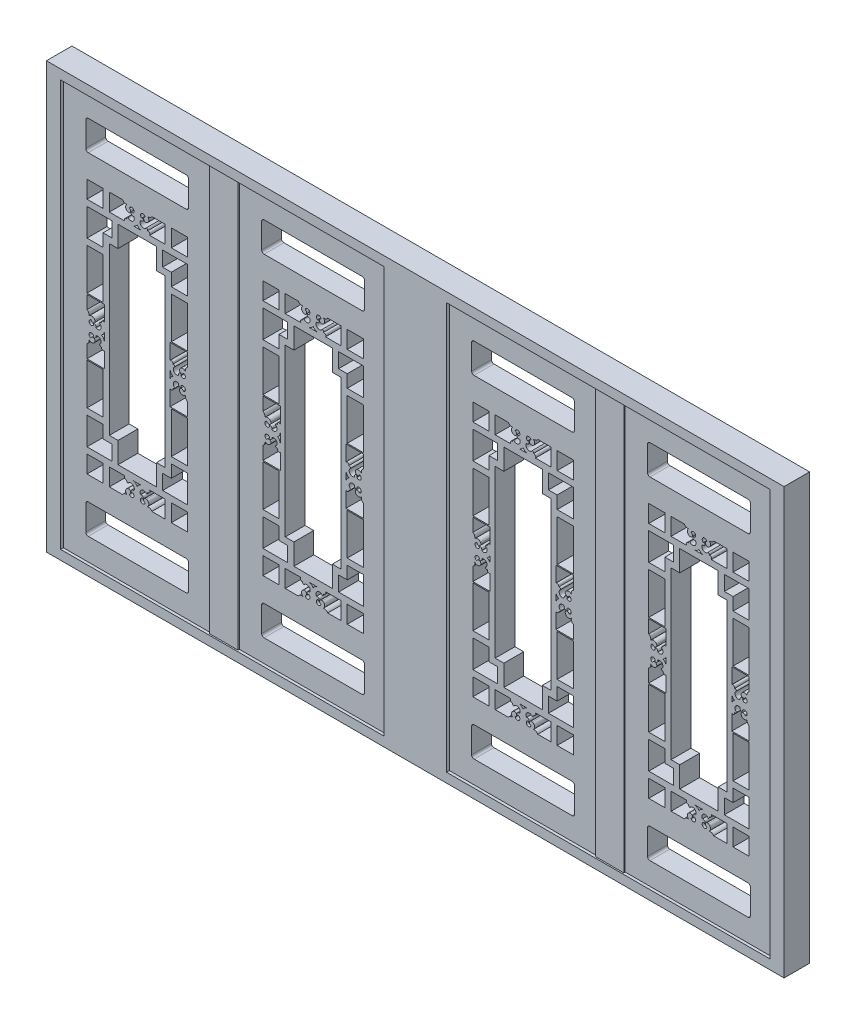
SolidWorks part; units mm, degrees
material "松木"
ref_plane "前视基准面" through (0, 0, 0) normal (0, 0, 1) x (1, 0, 0)
ref_plane "上视基准面" through (0, 0, 0) normal (0, 1, 0) x (1, 0, 0)
ref_plane "右视基准面" through (0, 0, 0) normal (1, 0, 0) x (0, 0, -1)
sketch "Sketch1" plane through (0, 0, 0) normal (0, 0, 1) x (1, 0, 0)
  line L0 (0, 0) -> (0, 1640)
  line L1 (0, 1640) -> (595, 1640)
  line L2 (595, 1640) -> (595, 0)
  line L3 (595, 0) -> (0, 0)
  dimension "D1" = 1640
  dimension "D2" = 595
extrude "Boss-Extrude1" add sketch "Sketch1" along normal blind 180
sketch "Sketch2" plane through (0, 0, 0) normal (0, 0, -1) x (-1, 0, 0)
  line L0 (-525, 1570) -> (-525, 70)
  line L1 (-525, 70) -> (-70, 70)
  line L2 (-70, 70) -> (-70, 1570)
  line L3 (-70, 1570) -> (-525, 1570)
  line L4 (-595, 0) -> (-595, 1640) construction
  line L5 (-595, 1640) -> (0, 1640) construction
  line L6 (-70, 1410) -> (-525, 1410)
  line L7 (-525, 230) -> (-70, 230)
  line L8 (-70, 1360) -> (-525, 1360)
  line L9 (-70, 280) -> (-525, 280)
  line L10 (-500, 1335) -> (-500, 305)
  line L11 (-500, 305) -> (-95, 305)
  line L12 (-95, 305) -> (-95, 1335)
  line L13 (-95, 1335) -> (-500, 1335)
  line L14 (-95, 1265) -> (-500, 1265)
  line L15 (-95, 1240) -> (-500, 1240)
  line L16 (-95, 375) -> (-500, 375)
  line L17 (-95, 400) -> (-500, 400)
  line L18 (-160, 1335) -> (-160, 1265)
  line L19 (-435, 1335) -> (-435, 1265)
  line L20 (-410, 1335) -> (-410, 1265)
  line L21 (-185, 1335) -> (-185, 1265)
  line L22 (-435, 375) -> (-435, 305)
  line L23 (-410, 375) -> (-410, 305)
  line L24 (-160, 375) -> (-160, 305)
  line L25 (-185, 375) -> (-185, 305)
  line L26 (-195, 400) -> (-195, 460)
  line L27 (-195, 460) -> (-160, 460)
  line L28 (-160, 460) -> (-160, 1180)
  line L29 (-160, 1180) -> (-195, 1180)
  line L30 (-195, 1180) -> (-195, 1240)
  line L31 (-400, 1240) -> (-400, 1180)
  line L32 (-400, 1180) -> (-435, 1180)
  line L33 (-435, 1180) -> (-435, 460)
  line L34 (-435, 460) -> (-400, 460)
  line L35 (-400, 460) -> (-400, 400)
  line L36 (-220, 1240) -> (-220, 1155)
  line L37 (-220, 1155) -> (-185, 1155)
  line L38 (-185, 1155) -> (-185, 485)
  line L39 (-185, 485) -> (-220, 485)
  line L40 (-220, 485) -> (-220, 400)
  line L41 (-375, 1240) -> (-375, 1155)
  line L42 (-375, 1155) -> (-410, 1155)
  line L43 (-410, 1155) -> (-410, 485)
  line L44 (-410, 485) -> (-375, 485)
  line L45 (-375, 485) -> (-375, 400)
  line L46 (-435, 1129) -> (-500, 1129)
  line L47 (-435, 1104) -> (-500, 1104)
  line L48 (-160, 1129) -> (-95, 1129)
  line L49 (-160, 1104) -> (-95, 1104)
  line L50 (-435, 511) -> (-500, 511)
  line L51 (-435, 536) -> (-500, 536)
  line L52 (-160, 511) -> (-95, 511)
  line L53 (-160, 536) -> (-95, 536)
  line L54 (-435, 937) -> (-500, 937)
  line L55 (-435, 919.4131) -> (-500, 919.4131)
  line L56 (-435, 703) -> (-500, 703)
  line L57 (-435, 728) -> (-500, 728)
  line L58 (-160, 919.4131) -> (-95, 919.4131)
  line L59 (-160, 937) -> (-95, 937)
  line L60 (-160, 703) -> (-95, 703)
  line L61 (-160, 728) -> (-95, 728)
  line L62 (-495, 210) -> (-100, 210)
  line L63 (-90, 200) -> (-90, 100)
  line L64 (-100, 90) -> (-495, 90)
  line L65 (-505, 100) -> (-505, 200)
  line L67 (-495, 1550) -> (-100, 1550)
  line L68 (-505, 1540) -> (-505, 1440)
  line L69 (-495, 1430) -> (-100, 1430)
  line L70 (-90, 1540) -> (-90, 1440)
  arc A0 (-495, 210) -> (-505, 200) centre (-495, 200) ccw
  arc A1 (-90, 200) -> (-100, 210) centre (-100, 200) ccw
  arc A2 (-505, 100) -> (-495, 90) centre (-495, 100) ccw
  arc A3 (-100, 90) -> (-90, 100) centre (-100, 100) ccw
  arc A4 (-495, 1550) -> (-505, 1540) centre (-495, 1540) ccw
  arc A5 (-90, 1540) -> (-100, 1550) centre (-100, 1540) ccw
  arc A6 (-505, 1440) -> (-495, 1430) centre (-495, 1440) ccw
  arc A7 (-100, 1430) -> (-90, 1440) centre (-100, 1440) ccw
  point P62 (-177.5, 1180)
  point P63 (-220, 442.5)
  point P64 (-177.5, 460)
  point P71 (-392.5, 485)
  dimension "D53" = 20
  dimension "D56" = 20
  dimension "D57" = 20
  dimension "D58" = 20
  dimension "D47" = 30
  dimension "D63" = 20
  dimension "D64" = 20
  dimension "D65" = 20
  dimension "D66" = 20
  dimension "D1" = 70
  dimension "D2" = 70
  dimension "D3" = 1500
  dimension "D4" = 455
  dimension "D5" = 160
  dimension "D6" = 160
  dimension "D7" = 50
  dimension "D8" = 50
  dimension "D9" = 25
  dimension "D10" = 25
  dimension "D11" = 25
  dimension "D12" = 25
  dimension "D13" = 70
  dimension "D14" = 25
  dimension "D15" = 25
  dimension "D16" = 70
  dimension "D17" = 65
  dimension "D18" = 65
  dimension "D19" = 25
  dimension "D20" = 25
  dimension "D21" = 100
  dimension "D22" = 100
  dimension "D23" = 60
  dimension "D24" = 60
  dimension "D25" = 35
  dimension "D26" = 35
  dimension "D27" = 100
  dimension "D28" = 35
  dimension "D29" = 60
  dimension "D30" = 60
  dimension "D31" = 25
  dimension "D32" = 25
  dimension "D33" = 25
  dimension "D34" = 25
  dimension "D35" = 25
  dimension "D36" = 25
  dimension "D37" = 25
  dimension "D38" = 25
  dimension "D39" = 111
  dimension "D40" = 25
  dimension "D41" = 111
  dimension "D42" = 25
  dimension "D43" = 167
  dimension "D44" = 17.5869
  dimension "D45" = 25
  dimension "D46" = 167
  dimension "D48" = 30
  dimension "D49" = 20
  dimension "D50" = 30
  dimension "D51" = 10
  dimension "D52" = 10
  dimension "D54" = 10
  dimension "D55" = 10
  dimension "D59" = 20
  dimension "D60" = 20
  dimension "D61" = 20
  dimension "D62" = 20
  dimension "D67" = 30
  dimension "D68" = 30
  dimension "D69" = 30
  dimension "D70" = 30
  dimension "D71" = 30
  dimension "D72" = 30
  dimension "D73" = 30
  dimension "D74" = 30
sketch "草图1" plane through (0, 0, 0) normal (0, 0, -1) x (-1, 0, 0)
  line L0 (-500, 305) -> (-95, 305) construction
  line L1 (-95, 375) -> (-500, 375) construction
  line L2 (-410, 375) -> (-410, 305) construction
  line L3 (-185, 375) -> (-185, 305) construction
  line L6 (-347.4491, 375) -> (-315.5, 375)
  line L7 (-279.5, 375) -> (-247.5509, 375)
  line L8 (-356.6733, 305) -> (-238.3267, 305)
  line L9 (-347.4491, 375) -> (-410, 375)
  line L10 (-410, 375) -> (-410, 305)
  line L11 (-410, 305) -> (-356.6733, 305)
  line L12 (-315.5, 375) -> (-279.5, 375)
  line L13 (-238.3267, 305) -> (-185, 305)
  line L14 (-185, 305) -> (-185, 375)
  line L15 (-185, 375) -> (-247.5509, 375)
  line L16 (-500, 707.5) -> (-430, 707.5)
  line L18 (-430, 802) -> (-430, 838)
  line L19 (-430, 707.5) -> (-430, 770.0509)
  line L20 (-430, 932.5) -> (-500, 932.5)
  line L22 (-500, 760.8267) -> (-500, 707.5)
  line L24 (-430, 869.9491) -> (-430, 932.5)
  line L25 (-500, 932.5) -> (-500, 879.1733)
  line L26 (-500, 879.1733) -> (-500, 1640) construction
  line L27 (-595, 707.5) -> (0, 707.5) construction
  line L28 (-595, 0) -> (-595, 1640) construction
  line L29 (0, 1640) -> (0, 0) construction
  line L30 (-500, 0) -> (-500, 760.8267) construction
  line L31 (0, 0) -> (-595, 0) construction
  line L32 (-595, 1640) -> (0, 1640) construction
  arc A0 (-297.5, 362.9626) -> (-315.5, 375) centre (-316.8257, 353.5409) ccw
  arc A1 (-279.5, 375) -> (-297.5, 362.9626) centre (-278.1743, 353.5409) ccw
  arc A2 (-311.5772, 341.0539) -> (-334.4772, 355.321) centre (-322.7578, 348.6199) ccw
  arc A4 (-260.5228, 355.321) -> (-283.4228, 341.0539) centre (-272.2422, 348.6199) ccw
  arc A5 (-347.4491, 375) -> (-339.4787, 363.4423) centre (-341.29, 370.7203) ccw
  arc A6 (-255.5213, 363.4423) -> (-247.5509, 375) centre (-253.71, 370.7203) ccw
  arc A7 (-339.4787, 363.4423) -> (-334.4772, 355.321) centre (-333.2172, 361.6977) ccw
  arc A8 (-260.5228, 355.321) -> (-255.5213, 363.4423) centre (-261.7828, 361.6977) ccw
  arc A9 (-297.5, 336.0027) -> (-311.5772, 341.0539) centre (-304.7324, 337.9882) ccw
  arc A10 (-283.4228, 341.0539) -> (-297.5, 336.0027) centre (-290.2676, 337.9882) ccw
  arc A11 (-311.5772, 341.0539) -> (-320.3587, 328.3114) centre (-314.2948, 333.5296) ccw
  arc A12 (-274.6413, 328.3114) -> (-283.4228, 341.0539) centre (-280.7052, 333.5296) ccw
  arc A13 (-315.214, 331.0064) -> (-320.3587, 328.3114) centre (-316.5099, 327.2221) ccw
  arc A14 (-274.6413, 328.3114) -> (-279.786, 331.0064) centre (-278.4901, 327.2221) ccw
  arc A16 (-279.786, 331.0064) -> (-265.6848, 320.9352) centre (-275, 322.8) ccw
  arc A17 (-329.3152, 320.9352) -> (-334.7689, 337.0364) centre (-332, 329) ccw
  arc A18 (-260.2311, 337.0364) -> (-265.6848, 320.9352) centre (-263, 329) ccw
  arc A19 (-329.3152, 320.9352) -> (-315.214, 331.0064) centre (-320, 322.8) ccw
  arc A20 (-463.9461, 834.0772) -> (-476.6886, 842.8587) centre (-471.4704, 836.7948) ccw
  arc A21 (-334.7689, 337.0364) -> (-338.5296, 312.5413) centre (-330.2084, 323.8) ccw
  arc A23 (-338.5296, 312.5413) -> (-356.6733, 305) centre (-343, 297.7) ccw
  arc A24 (-238.3267, 305) -> (-256.4704, 312.5413) centre (-252, 297.7) ccw
  arc A25 (-256.4704, 312.5413) -> (-260.2311, 337.0364) centre (-264.7916, 323.8) ccw
  arc A26 (-473.9936, 837.714) -> (-476.6886, 842.8587) centre (-477.7779, 839.0099) ccw
  arc A27 (-463.9461, 805.9228) -> (-462.5046, 806.773) centre (-467.0118, 812.7676) ccw
  arc A28 (-484.0648, 851.8152) -> (-467.9636, 857.2689) centre (-476, 854.5) ccw
  arc A29 (-430, 869.9491) -> (-441.5577, 861.9787) centre (-434.2797, 863.79) ccw
  arc A30 (-467.9636, 857.2689) -> (-492.4587, 861.0296) centre (-481.2, 852.7084) ccw
  arc A31 (-442.0374, 820) -> (-430, 838) centre (-451.4591, 839.3257) ccw
  arc A32 (-441.5577, 861.9787) -> (-449.679, 856.9772) centre (-443.3023, 855.7172) ccw
  arc A33 (-467.9636, 782.7311) -> (-484.0648, 788.1848) centre (-476, 785.5) ccw
  arc A34 (-476.6886, 797.1413) -> (-463.9461, 805.9228) centre (-471.4704, 803.2052) ccw
  arc A35 (-476.6886, 797.1413) -> (-473.9936, 802.286) centre (-477.7779, 800.9901) ccw
  arc A36 (-441.5577, 778.0213) -> (-430, 770.0509) centre (-434.2797, 776.21) ccw
  arc A37 (-492.4587, 778.9704) -> (-467.9636, 782.7311) centre (-481.2, 787.2916) ccw
  arc A38 (-449.679, 783.0228) -> (-463.9461, 805.9228) centre (-456.3801, 794.7422) ccw
  arc A39 (-484.0648, 851.8152) -> (-473.9936, 837.714) centre (-482.2, 842.5) ccw
  arc A40 (-500, 760.8267) -> (-492.4587, 778.9704) centre (-507.3, 774.5) ccw
  arc A41 (-449.679, 783.0228) -> (-441.5577, 778.0213) centre (-443.3023, 784.2828) ccw
  arc A42 (-473.9936, 802.286) -> (-484.0648, 788.1848) centre (-482.2, 797.5) ccw
  arc A43 (-463.9461, 834.0772) -> (-449.679, 856.9772) centre (-456.3801, 845.2578) ccw
  arc A44 (-492.4587, 861.0296) -> (-500, 879.1733) centre (-507.3, 865.5) ccw
  arc A46 (-430, 802) -> (-442.0374, 820) centre (-451.4591, 800.6743) ccw
  arc A48 (-462.5046, 833.227) -> (-463.9461, 834.0772) centre (-467.0118, 827.2324) ccw
  dimension "D5" = 37.0118
  dimension "D6" = 105.2676
  dimension "D11" = 27
  dimension "D12" = 27
  dimension "D13" = 15
  dimension "D10" = 15
  dimension "D15" = 13
  dimension "D16" = 13
  dimension "D2" = 15
  dimension "D3" = 15
  dimension "D8" = 16
  dimension "D9" = 16
  dimension "D18" = 8
  dimension "D19" = 8
  dimension "D24" = 9.5
  dimension "D25" = 19
  dimension "D30" = 17
  dimension "D31" = 17
  dimension "D36" = 28
  dimension "D37" = 95
  dimension "D40" = 31
  dimension "D41" = 31
  dimension "D4" = 37.0118
  dimension "D7" = 105.2676
  dimension "D14" = 95.7052
  dimension "D17" = 95.7052
  dimension "D20" = 47.7779
  dimension "D21" = 47.7779
  dimension "D22" = 93.4901
  dimension "D23" = 93.4901
  dimension "D26" = 90
  dimension "D27" = 90
  dimension "D28" = 52.2
  dimension "D29" = 52.2
  dimension "D32" = 24
  dimension "D33" = 24
  dimension "D34" = 78
  dimension "D35" = 78
  dimension "D38" = 18.8
  dimension "D39" = 707.5
  dimension "D42" = 7.3
  dimension "D43" = 7.3
  dimension "D44" = 67
  dimension "D45" = 67
sketch "草图5" plane through (0, 0, 0) normal (0, 0, -1) x (-1, 0, 0)
sketch "草图6" plane through (0, 0, 180) normal (0, 0, 1) x (1, 0, 0)
  line L0 (0, 1640) -> (0, 0)
  line L1 (0, 0) -> (595, 0)
  line L2 (595, 0) -> (595, 1640)
  line L3 (595, 1640) -> (0, 1640)
extrude "切除-拉伸2" cut sketch "草图6" against normal blind 100
extrude "切除-拉伸3" cut sketch "草图1" against normal blind 100 contours A23 A21 A17 A19 A13 A11 A9 A2 A7 A5 L9 L10 L11 | A25 A24 L13 L14 L15 A6 A8 A4 A10 A12 A14 A16 A18 | A1 L12 A0 region at (368.1315, 340.5137, 0) region at (297.5, 371.6597, 0) region at (226.8685, 340.5137, 0)
extrude "切除-拉伸5" cut sketch "Sketch2" against normal through all contours L64 A3 L63 A1 L62 A0 L65 A2 | L22 L16 L10 L11 | L16 L24 L11 L12 | L33 L50 L10 L17 L35 L34 | L52 L28 L27 L26 L17 L12 | L33 L56 L10 L51 | L60 L28 L53 L12 | L44 L45 L17 L40 L39 L38 L37 L36 L15 L41 L42 L43 | L54 L33 L47 L10 | L28 L59 L12 L49 | L28 L48 L12 L15 L30 L29 | L13 L18 L14 L12 | L19 L13 L10 L14 | L46 L33 L32 L31 L15 L10 | L69 A7 L70 A5 L67 A4 L68 A6 region at (467.5, 1300, 0) region at (456.2279, 1190.2488, 0) region at (467.5, 1020.5, 0) region at (297.5, 820, 0) region at (127.5, 1300, 0) region at (138.7721, 1190.2488, 0) region at (467.5, 619.5, 0) region at (127.5, 1020.5, 0) region at (456.2279, 449.7512, 0) region at (138.7721, 449.7512, 0) region at (467.5, 340, 0) region at (127.5, 619.5, 0) region at (127.5, 340, 0) region at (297.5, 150, 0) region at (297.5, 1490, 0)
ref_plane "基准面1" through (0, 820, 0) normal (0, 1, 0) x (1, 0, 0)
mirror "镜向1" about plane through (0, 820, 0) normal (0, 1, 0) of "切除-拉伸3"
extrude "切除-拉伸8" cut sketch "草图1<5>" against normal through all contours A48 A43 A32 A29 L24 L20 L25 A44 A30 A28 A39 A26 A20 | A35 A42 A33 A37 A40 L22 L16 L19 A36 A41 A38 A27 A34 | A31 L18 A46 region at (464.4863, 749.3685, 0) region at (464.4863, 890.6315, 0)
sketch "草图1<5>" plane through (0, 0, 0) normal (0, 0, -1) x (-1, 0, 0) same geometry as "草图1"
ref_plane "基准面3" through (297.5, 0, 0) normal (-1, 0, 0) x (0, 0, 1)
mirror "镜向3" about plane through (297.5, 0, 0) normal (-1, 0, 0) of "切除-拉伸8"
scale "缩放比例1" bodies to scale 117 scale about centroid uniform scaling yes scale factor 0.87395
pattern_linear "阵列(线性)7" count 2 spacing 620 along (-1, 0, 0) of bodies 118
pattern_linear "阵列(线性)8" count 2 spacing 1360 along (-1, 0, 0) of bodies 118 130
sketch "草图10" plane through (0, 0, 74.958) normal (0, 0, 1) x (1, 0, 0)
  line L0 (-1942.5, 1536.6387) -> (-1942.5, 103.3613) construction
  line L1 (-1992.5, 1570.0013) -> (607.5, 1570.0013)
  line L2 (-1992.5, 1570.0013) -> (-1992.5, 70.0013)
  line L3 (-1992.5, 70.0013) -> (607.5, 70.0013)
  line L4 (607.5, 1570.0013) -> (607.5, 70.0013)
  line L5 (-1942.5, 103.3613) -> (-1422.5, 103.3613) construction
  line L7 (-1942.5, 1536.6387) -> (-802.5, 1536.6387)
  line L8 (-1942.5, 1536.6387) -> (-1942.5, 103.3613)
  line L9 (-1942.5, 103.3613) -> (-802.5, 103.3613)
  line L10 (-802.5, 1536.6387) -> (-802.5, 103.3613)
  line L11 (-582.5, 1536.6387) -> (557.5, 1536.6387)
  line L12 (-582.5, 1536.6387) -> (-582.5, 103.3613)
  line L13 (-582.5, 103.3613) -> (557.5, 103.3613)
  line L14 (557.5, 1536.6387) -> (557.5, 103.3613)
  dimension "D1" = 2600
  dimension "D2" = 50
  dimension "D3" = 1500
  dimension "D4" = 33.36
extrude "凸台-拉伸3" add sketch "草图10" along normal blind 10 and the other way blind 79.92
sketch "草图11" plane through (0, 0, 74.958) normal (0, 0, 1) x (1, 0, 0)
  line L1 (-1422.5, 1536.6387) -> (-1322.5, 1536.6387)
  line L2 (-1422.5, 1536.6387) -> (-1422.5, 103.3613)
  line L3 (-1422.5, 103.3613) -> (-1322.5, 103.3613)
  line L4 (-1322.5, 1536.6387) -> (-1322.5, 103.3613)
  line L5 (-62.5, 1536.6387) -> (37.5, 1536.6387)
  line L6 (-62.5, 1536.6387) -> (-62.5, 103.3613)
  line L7 (-62.5, 103.3613) -> (37.5, 103.3613)
  line L8 (37.5, 1536.6387) -> (37.5, 103.3613)
extrude "凸台-拉伸4" add sketch "草图11" along normal blind 5 and the other way blind 74.92 contours L2 L1 L4 L3 | L6 L5 L8 L7
